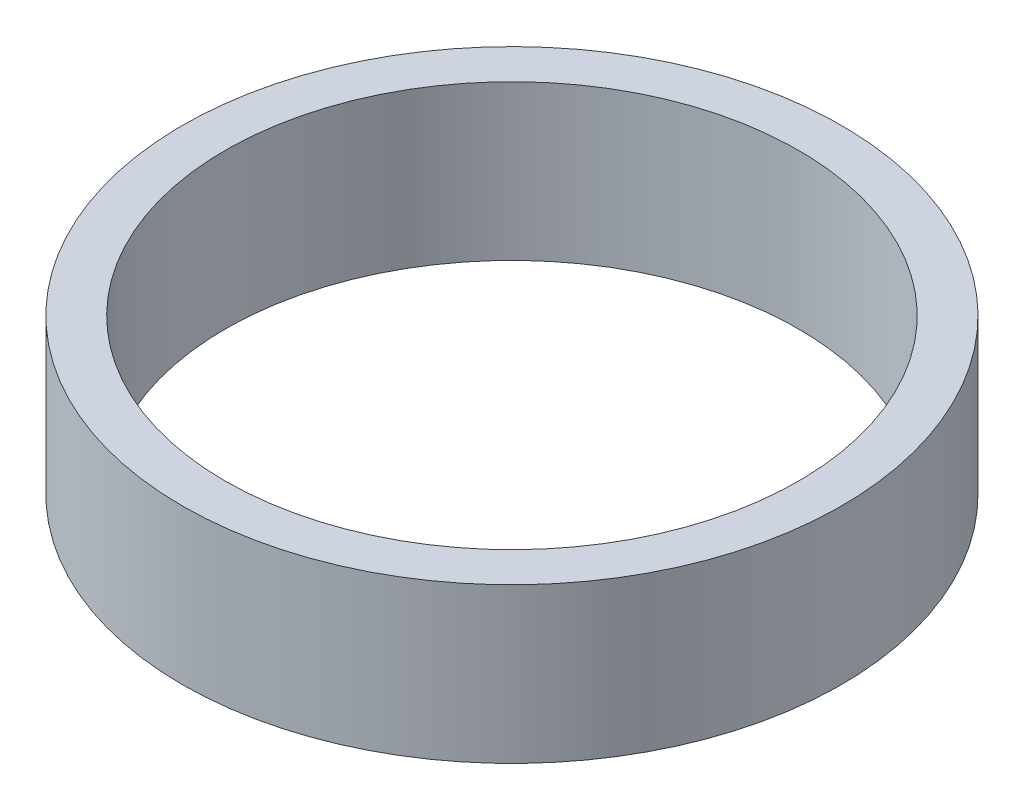
SolidWorks part; units mm, degrees
ref_plane "Front Plane" through (0, 0, 0) normal (0, 0, 1) x (1, 0, 0)
ref_plane "Top Plane" through (0, 0, 0) normal (0, 1, 0) x (1, 0, 0)
ref_plane "Right Plane" through (0, 0, 0) normal (1, 0, 0) x (0, 0, -1)
sketch "Sketch1" plane through (0, 0, 0) normal (0, 1, 0) x (1, 0, 0)
  circle A0 centre (0, 0) radius 57.5
  dimension "FLANGE_OD" = 115
extrude "Boss-Extrude1" add sketch "Sketch1" along normal blind 27
sketch "Sketch2" plane through (0, 0, 0) normal (0, 1, 0) x (1, 0, 0)
  circle A0 centre (0, 0) radius 50
  dimension "BORE_D" = 100
extrude "Cut-Extrude1" cut sketch "Sketch2" along normal through all
sketch "Sketch3" plane through (0, 27, 0) normal (0, 1, 0) x (1, 0, 0)
  circle A0 centre (0, 0) radius 26.4441 construction
  circle A1 centre (-26.4441, 0) radius 1.5
  dimension "BOLT_D" = 3
  dimension "BOLT_PCD" = 52.8882
extrude "Cut-Extrude2" cut sketch "Sketch3" against normal blind 17.1189 rebuild error yes
pattern_circular "CirPattern1" count 5 over 360 rebuild error yes
